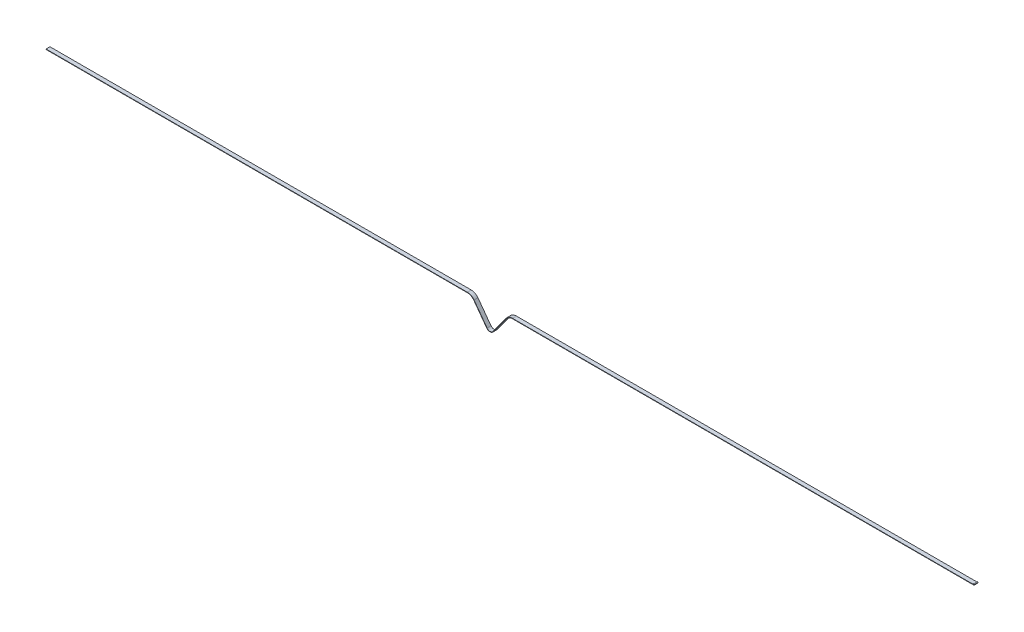
SolidWorks part; units mm, degrees
ref_plane "Front Plane" through (0, 0, 0) normal (0, 0, 1) x (1, 0, 0)
ref_plane "Top Plane" through (0, 0, 0) normal (0, 1, 0) x (1, 0, 0)
ref_plane "Right Plane" through (0, 0, 0) normal (1, 0, 0) x (0, 0, -1)
sketch "Sketch1" plane through (0, 0, 0) normal (1, 0, 0) x (0, 0, -1)
  line L1 (0, 0) -> (6, 0)
  line L2 (0, 0) -> (0, 0.63)
  line L3 (0, 0.63) -> (6, 0.63)
  line L4 (6, 0) -> (6, 0.63)
  dimension "D1" = 0.63
  dimension "D2" = 6
sketch "Sketch2" plane through (0, 0, 0) normal (0, 0, 1) x (1, 0, 0)
  line L0 (0, 0) -> (-707.3697, 0)
  line L1 (-717.0024, -4.8779) -> (-737.0146, -32.1359)
  line L2 (-746.8649, -32.1359) -> (-766.8771, -4.8779)
  line L3 (-776.5097, 0) -> (-1422.4, 0)
  arc A0 (-707.3697, 0) -> (-717.0024, -4.8779) centre (-707.3697, -11.95) ccw
  arc A1 (-737.0146, -32.1359) -> (-746.8649, -32.1359) centre (-741.9397, -28.52) cw
  arc A2 (-766.8771, -4.8779) -> (-776.5097, 0) centre (-776.5097, -11.95) ccw
  circle A3 centre (-776.5097, -11.95) radius 11.95 construction
  circle A4 centre (-741.9397, -28.52) radius 6.11 construction
  circle A5 centre (-707.3697, -11.95) radius 11.95 construction
  dimension "D1" = 6.11
  dimension "D4" = 1422.4
sweep "Sweep1" add profiles "Sketch1" path "Sketch2"
sketch "Sketch3" plane through (0, 0, 0) normal (0, 0, 1) x (1, 0, 0)
  line L0 (0, 0.63) -> (-707.3697, 0.63) construction
  line L1 (-1.5, 0.63) -> (-1.5, 0)
  line L2 (0, 0) -> (-707.3697, 0) construction
  line L3 (-1.5, 0) -> (0, 0)
  line L4 (0, 0) -> (0, 0.63)
  arc A1 (0, 0.63) -> (-1.5, 0.63) centre (-0.75, 0.63) ccw
  dimension "D1" = 0.75
extrude "Boss-Extrude1" add sketch "Sketch3" against normal through all
pattern_curve "CrvPattern1" [suppressed] of bodies 102 driven by "Sketch2" parameters "D1"=2000, "D3"=2, "D2"=1, "D4"=10
